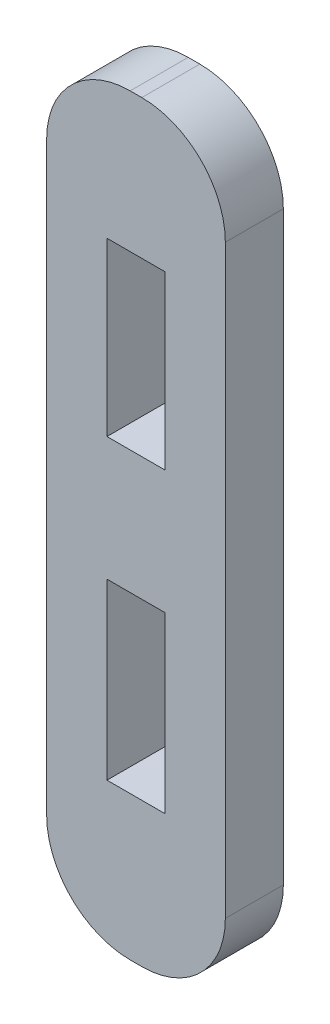
SolidWorks part; units mm, degrees
ref_plane "Front Plane" through (0, 0, 0) normal (0, 0, 1) x (1, 0, 0)
ref_plane "Top Plane" through (0, 0, 0) normal (0, 1, 0) x (1, 0, 0)
ref_plane "Right Plane" through (0, 0, 0) normal (1, 0, 0) x (0, 0, -1)
sketch "Sketch1" plane through (0, 0, 0) normal (0, 0, 1) x (1, 0, 0)
  line L0 (3.2385, 18.9437) -> (1.651, 18.9437) construction
  line L1 (0, 0) -> (4.8895, 0)
  line L2 (0, 0) -> (0, 20.5947)
  line L3 (0, 20.5947) -> (4.8895, 20.5947)
  line L4 (4.8895, 0) -> (4.8895, 20.5947)
  line L7 (3.2385, 16.7847) -> (3.2385, 18.9437) construction
  dimension "D1" = 1.651
  dimension "D2" = 1.651
extrude "Boss-Extrude1" add sketch "Sketch1" along normal blind 1.5875
sketch "Sketch2" plane through (0, 0, 0) normal (0, 0, -1) x (-1, 0, 0)
  line L1 (-3.2385, 14.2447) -> (-3.2385, 12.0857)
  line L2 (-3.2385, 12.0857) -> (-1.651, 12.0857)
  line L3 (-1.651, 12.0857) -> (-1.651, 14.2447)
  line L4 (-1.651, 15.7282) -> (-1.651, 18.6121) construction
  line L6 (-1.651, 16.7847) -> (-1.651, 18.9437) construction
  line L7 (-3.2385, 15.7282) -> (-3.2385, 18.6121) construction
  line L8 (-1.651, 5.227) -> (-1.651, 6.4145) construction
  line L9 (-3.2385, 5.227) -> (-3.2385, 4.8666) construction
  line L10 (-3.2385, 16.7847) -> (-1.651, 16.7847) construction
  line L11 (-3.2385, 6.4145) -> (-3.2385, 5.227) construction
  line L12 (-1.651, 4.8666) -> (-1.651, 5.227) construction
  line L13 (-1.651, 5.227) -> (-1.651, 6.4145)
  line L14 (-1.651, 15.4009) -> (-1.651, 15.7282) construction
  line L15 (-1.651, 14.2447) -> (-1.651, 15.4009) construction
  line L16 (-3.2385, 16.7847) -> (-1.651, 16.7847)
  line L17 (-3.2385, 15.7282) -> (-3.2385, 15.4009) construction
  line L18 (-3.2385, 15.4009) -> (-3.2385, 14.2447) construction
  line L19 (-1.651, 15.7282) -> (-1.651, 16.7847)
  line L20 (-3.2385, 5.227) -> (-3.2385, 4.8666)
  line L21 (-3.2385, 6.4145) -> (-3.2385, 5.227)
  line L22 (-3.2385, 3.9426) -> (-1.651, 3.9426) construction
  line L25 (-3.2385, 15.7282) -> (-3.2385, 16.7847)
  line L26 (-1.651, 15.4009) -> (-1.651, 15.7282)
  line L27 (-1.651, 14.2447) -> (-1.651, 15.4009)
  line L28 (-3.2385, 15.7282) -> (-3.2385, 15.4009)
  line L29 (-3.2385, 3.9426) -> (-1.651, 3.9426)
  line L30 (-1.651, 4.8666) -> (-1.651, 5.227)
  line L31 (-1.651, 1.9826) -> (-1.651, 4.8666) construction
  line L32 (-3.2385, 15.4009) -> (-3.2385, 14.2447)
  line L33 (-3.2385, 6.4145) -> (-3.2385, 8.7061)
  line L34 (-3.2385, 8.7061) -> (-1.651, 8.7061)
  line L35 (-1.651, 8.7061) -> (-1.651, 6.4145)
  line L36 (-1.651, 3.9426) -> (-1.651, 1.651) construction
  line L37 (-0.8554, 16.7847) -> (-0.8554, 18.9437) construction
  line L38 (-3.2385, 1.9826) -> (-3.2385, 4.8666) construction
  line L39 (-1.651, 3.9426) -> (-1.651, 4.8666)
  line L40 (-3.2385, 3.9426) -> (-3.2385, 4.8666)
  line L41 (-0.8554, 1.651) -> (-0.8554, 3.9426) construction
extrude "Cut-Extrude1" cut sketch "Sketch2" against normal through all
fillet "Fillet1" radius 2.286 4 edges at (0, 0, 0.7937) (4.8895, 0, 0.7937) (4.8895, 20.5947, 0.7937) (0, 20.5947, 0.7937)
